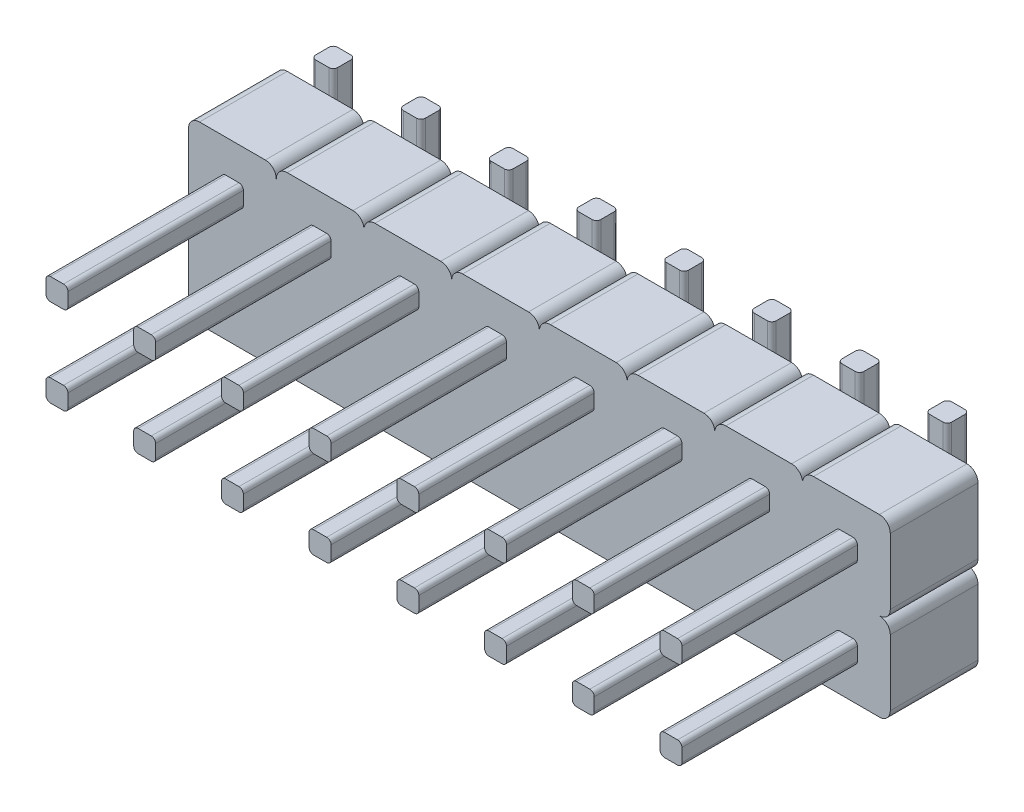
SolidWorks part; units mm, degrees
ref_plane "前视基准面" through (0, 0, 0) normal (0, 0, 1) x (1, 0, 0)
ref_plane "上视基准面" through (0, 0, 0) normal (0, 1, 0) x (1, 0, 0)
ref_plane "右视基准面" through (0, 0, 0) normal (1, 0, 0) x (0, 0, -1)
sketch "草图1" plane through (0, 0, 0) normal (0, 0, 1) x (1, 0, 0)
  line L0 (1, 0) -> (1, -2) construction
  line L1 (0.25, 0) -> (1.75, 0)
  line L2 (0, -0.25) -> (0, -1.75)
  line L3 (0.25, -2) -> (1.75, -2)
  line L4 (2, -0.25) -> (2, -1.75)
  line L5 (0, -1) -> (2, -1) construction
  line L7 (0.85, -0.75) -> (1.15, -0.75)
  line L8 (0.75, -0.85) -> (0.75, -1.15)
  line L9 (0.85, -1.25) -> (1.15, -1.25)
  line L10 (1.25, -0.85) -> (1.25, -1.15)
  arc A0 (2, -1.75) -> (1.75, -2) centre (1.75, -1.75) cw
  arc A1 (0.25, -2) -> (0, -1.75) centre (0.25, -1.75) cw
  arc A2 (0.25, 0) -> (0, -0.25) centre (0.25, -0.25) ccw
  arc A3 (2, -0.25) -> (1.75, 0) centre (1.75, -0.25) ccw
  circle A4 centre (1, -1) radius 0.25 construction
  arc A5 (0.75, -1.15) -> (0.85, -1.25) centre (0.85, -1.15) ccw
  arc A6 (1.15, -1.25) -> (1.25, -1.15) centre (1.15, -1.15) ccw
  arc A7 (1.25, -0.85) -> (1.15, -0.75) centre (1.15, -0.85) ccw
  arc A8 (0.85, -0.75) -> (0.75, -0.85) centre (0.85, -0.85) ccw
  point P11 (0, 0)
  dimension "D3" = 0.25
  dimension "D4" = 0.5
  dimension "D5" = 0.1
  dimension "D1" = 2
  dimension "D2" = 2
extrude "凸台-拉伸1" add sketch "草图1" along normal blind 2
sketch "草图2" plane through (0, 0, 2) normal (0, 0, 1) x (1, 0, 0)
  line L0 (0.75, -0.85) -> (0.75, -1.15)
  line L1 (0.85, -1.25) -> (1.15, -1.25)
  line L2 (1.25, -1.15) -> (1.25, -0.85)
  line L3 (1.15, -0.75) -> (0.85, -0.75)
  arc A0 (1.25, -1.15) -> (1.15, -1.25) centre (1.15, -1.15) cw
  arc A1 (0.85, -1.25) -> (0.75, -1.15) centre (0.85, -1.15) cw
  arc A2 (1.25, -0.85) -> (1.15, -0.75) centre (1.15, -0.85) ccw
  arc A3 (0.85, -0.75) -> (0.75, -0.85) centre (0.85, -0.85) ccw
  dimension "D1" = 0.1
extrude "凸台-拉伸2" add sketch "草图2" along normal blind 4 and the other way blind 2
pattern_linear "阵列(线性)2" count 8 spacing 2 along (1, 0, 0) count 2 spacing 2 along (0, -1, 0) of "凸台-拉伸1", "凸台-拉伸2"
sketch "草图3" plane through (0, 0, 0) normal (0, 0, -1) x (-1, 0, 0)
  line L0 (-1, 0) -> (-1, -4) construction
  line L1 (-1.75, 0) -> (-0.25, 0) construction
  line L2 (-0.25, -4) -> (-1.75, -4) construction
  line L3 (0, -1) -> (-2.4529, -1) construction
  line L4 (0, -0.25) -> (0, -1.75) construction
  line L5 (-0.25, -2) -> (-1.75, -2) construction
  line L9 (-0.75, -0.85) -> (-0.75, -1.15)
  line L10 (-0.85, -1.25) -> (-1.15, -1.25)
  line L11 (-1.25, -0.85) -> (-1.25, -1.15)
  line L12 (-0.85, -0.75) -> (-1.15, -0.75)
  arc A4 (-1.25, -1.15) -> (-1.15, -1.25) centre (-1.15, -1.15) ccw
  arc A5 (-0.75, -1.15) -> (-0.85, -1.25) centre (-0.85, -1.15) cw
  arc A6 (-0.85, -0.75) -> (-0.75, -0.85) centre (-0.85, -0.85) cw
  arc A7 (-1.15, -0.75) -> (-1.25, -0.85) centre (-1.15, -0.85) ccw
  point P26 (-1, -1.25)
  point P28 (-0.75, -1)
  point P29 (-1.25, -1)
  point P31 (-1.25, -1.25)
  point P34 (-0.75, -1.25)
  point P37 (-0.75, -0.75)
  point P40 (-1.25, -0.75)
  dimension "D4" = 0.1
  dimension "D2" = 0.5
  dimension "D3" = 0.5
ref_plane "基准面1" through (1, 0, 0) normal (-1, 0, 0) x (0, 0, 1)
sketch "草图4" plane through (1, 0, 0) normal (-1, 0, 0) x (0, 0, 1)
  line L0 (0, -1.2503) -> (-0.45, -1.2503)
  line L1 (-0.55, -1.1503) -> (-0.55, 0.5)
  line L2 (0, 0) -> (0, -4) construction
  line L3 (0, 0) -> (0, -2) construction
  line L5 (-1.9741, 0.5) -> (2.5979, 0.5) construction
  line L6 (2, 0) -> (0, 0) construction
  arc A0 (-0.45, -1.2503) -> (-0.55, -1.1503) centre (-0.45, -1.1503) cw
  dimension "D3" = 0.1
  dimension "D1" = 0.55
  dimension "D2" = 0.5
ref_plane "基准面2" through (0, -2, 0) normal (0, -1, 0) x (1, 0, 0)
sweep "扫描2" add profiles "草图3" path "草图4"
mirror "镜向5" about plane through (0, -2, 0) normal (0, -1, 0) of "扫描2"
pattern_linear "阵列(线性)10" count 8 spacing 2 along (1, 0, 0) of "扫描2", "镜向5"
